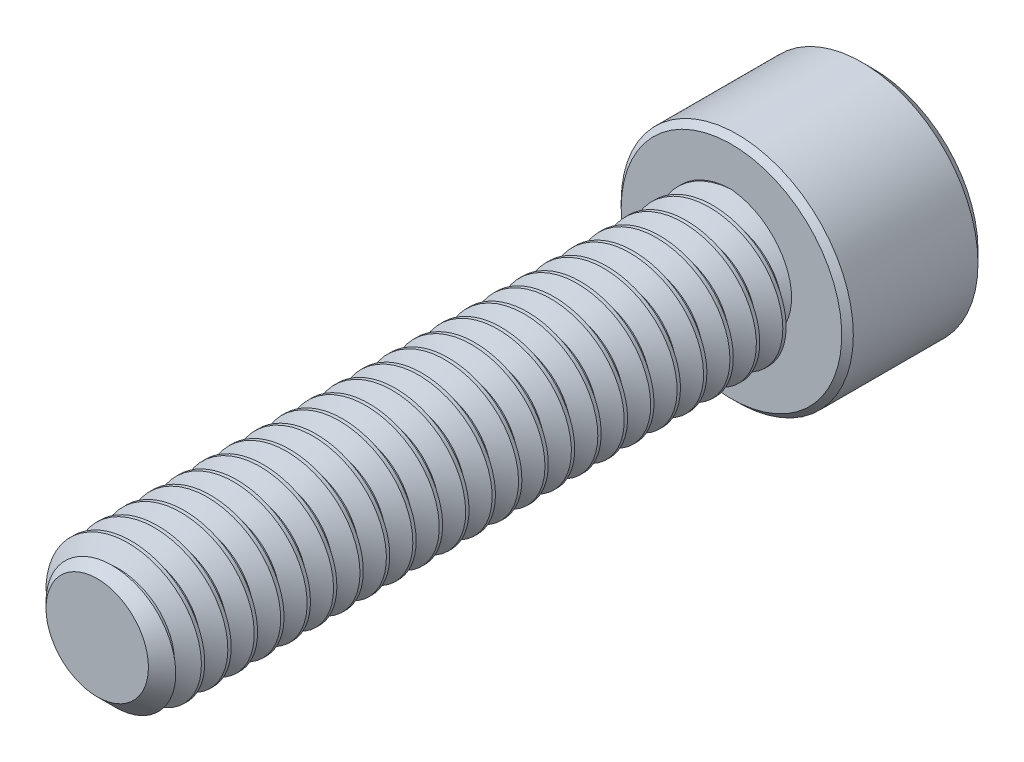
SolidWorks part; units mm, degrees
ref_plane "Front Plane" through (0, 0, 0) normal (0, 0, 1) x (1, 0, 0)
ref_plane "Top Plane" through (0, 0, 0) normal (0, 1, 0) x (1, 0, 0)
ref_plane "Right Plane" through (0, 0, 0) normal (1, 0, 0) x (0, 0, -1)
sketch "Sketch0" plane through (0, 0, 0) normal (1, 0, 0) x (0, 0, -1)
  line L0 (0, 0) -> (12.7, 0) construction
  point P2 (15.5448, 0)
  point P4 (0, 0)
  dimension "D1" = 12.7
  dimension "D2" = 2.8448
  dimension "Min Thread" = 0
sketch "Sketch1" plane through (0, 0, 0) normal (0, 0, 1) x (1, 0, 0)
  circle A0 centre (0, 0) radius 1.4224
  dimension "OD" = 2.8448
extrude "Extrude1" add sketch "Sketch1" against normal blind 12.7
sketch "Sketch2" plane through (0, 0, 0) normal (0, 0, 1) x (1, 0, 0)
  circle A0 centre (0, 0) radius 1.4224 construction
  circle A1 centre (0, 0) radius 1.4224
curve "Helix/Spiral1" pitch 0.5292 height 13.2292 turns 25 parameters "pitch"=0.5292
chamfer "Chamfer3" distance 0.3969 angle 45 1 edges at (1.4224, 0, 0)
sketch "Sketch3" plane through (0, 0, 0) normal (1, 0, 0) x (0, 0, -1)
  line L0 (-0.463, 1.4224) -> (-0.2646, 1.0787)
  line L1 (-0.2646, 1.0787) -> (-0.1984, 1.0787)
  line L2 (-0.1984, 1.0787) -> (0, 1.4224)
  line L3 (-0.463, 1.4224) -> (0, 1.4224)
  line L4 (-0.2315, 1.4224) -> (-0.2315, 1.0787) construction
  line L5 (-0.3638, 1.2505) -> (-0.0992, 1.2505) construction
  line L6 (0, 1.4224) -> (0, -1.4224) construction
  dimension "D1" = 0.0661
  dimension "D2" = 0.2646
  dimension "D3" = 60
sweep "Cut-Sweep1" cut profiles "Sketch3" path "Helix/Spiral1" align with end faces yes
sketch "Sketch5" plane through (0, 0, 0) normal (1, 0, 0) x (0, 0, -1)
  line L0 (12.7, -1.0872) -> (12.7, 1.0149) construction
  line L1 (12.7, 1.4224) -> (0, 1.4224)
  line L2 (12.7, 1.4224) -> (12.7, 0)
  line L3 (12.7, 0) -> (-0.5177, 0)
  line L4 (0, 0) -> (12.7, 0) construction
  line L5 (0, 1.4224) -> (-0.5177, 0)
  line L6 (0, 0) -> (15.24, 0) construction
  dimension "D1" = 70
  dimension "D3" = 2.54
revolve "partially thread" [suppressed] add sketch "Sketch5" angle 360 about L6
sketch "Sketch6" plane through (0, 0, -12.7) normal (0, 0, -1) x (-1, 0, 0)
  circle A0 centre (0, 0) radius 2.3241
  dimension "head dia" = 4.6482
extrude "Extrude2" add sketch "Sketch6" along normal blind 2.8448
sketch "Sketch7" plane through (0, 0, -15.5448) normal (0, 0, -1) x (-1, 0, 0)
  line L1 (0, 1.3748) -> (-1.1906, 0.6874)
  line L2 (-1.1906, 0.6874) -> (-1.1906, -0.6874)
  line L3 (-1.1906, -0.6874) -> (0, -1.3748)
  line L4 (0, -1.3748) -> (1.1906, -0.6874)
  line L5 (1.1906, -0.6874) -> (1.1906, 0.6874)
  line L6 (1.1906, 0.6874) -> (0, 1.3748)
  circle A0 centre (0, 0) radius 1.1906 construction
  dimension "hex dia" = 2.3813
extrude "Cut-Extrude1" cut sketch "Sketch7" against normal blind 1.7859
sketch "Sketch8" plane through (0, 0, -15.5448) normal (0, 0, -1) x (-1, 0, 0)
  circle A0 centre (0, 0) radius 1.3748
extrude "Cut-Extrude2" cut sketch "Sketch8" against normal through all draft 45
chamfer "Chamfer1" distance 0.2324 angle 45 1 edges at (-2.3241, 0, -15.5448)
chamfer "Chamfer2" distance 0.1162 angle 45 1 edges at (-2.3241, 0, -12.7)
sketch "Sketch9" plane through (0, 0, 0) normal (1, 0, 0) x (0, 0, -1)
  line L0 (0, 1.4224) -> (0, -1.4224) construction
  line L1 (1.3229, 1.4224) -> (1.3229, -1.4224) construction
  line L2 (15.5448, 2.3241) -> (15.5448, -2.3241) construction
  line L3 (12.7, 2.3241) -> (12.7, -2.3241) construction
  line L4 (12.7, 2.2079) -> (12.7, -2.2079) construction
  line L5 (15.5448, -2.0917) -> (15.5448, 2.0917) construction
  line L6 (12.7, -2.3241) -> (12.7, 2.3241) construction
  line L7 (0, 1.0255) -> (0, -1.0255) construction
  line L8 (-0.463, 1.4224) -> (0, 1.4224) construction
  line L9 (1.3229, 0) -> (0, 0) construction
  dimension "D1" = 1.3229
equation "\"D3@Helix/Spiral1\" = \"screw length@Extrude1\"+\"pitch@Helix/Spiral1\""
equation "\"D1@Sketch3\" = \"pitch@Helix/Spiral1\"*.125"
equation "\"D2@Sketch3\" = \"pitch@Helix/Spiral1\"*.5"
equation "\"D1@Cut-Extrude1\" = \"hex dia@Sketch7\"*.75"
equation "\"D1@Chamfer1\" = \"head dia@Sketch6\"*.05"
equation "\"D1@Sketch9\" = \"pitch@Helix/Spiral1\"*2.50"
equation "\"D1@Chamfer2\" = \"D1@Chamfer1\"/2"
equation "\"D1@Chamfer3\" = \"pitch@Helix/Spiral1\"*.750"
equation "\"D1@Sketch0\" = \"screw length@Extrude1\""
equation "\"D2@Sketch0\" = \"head depth@Extrude2\""
